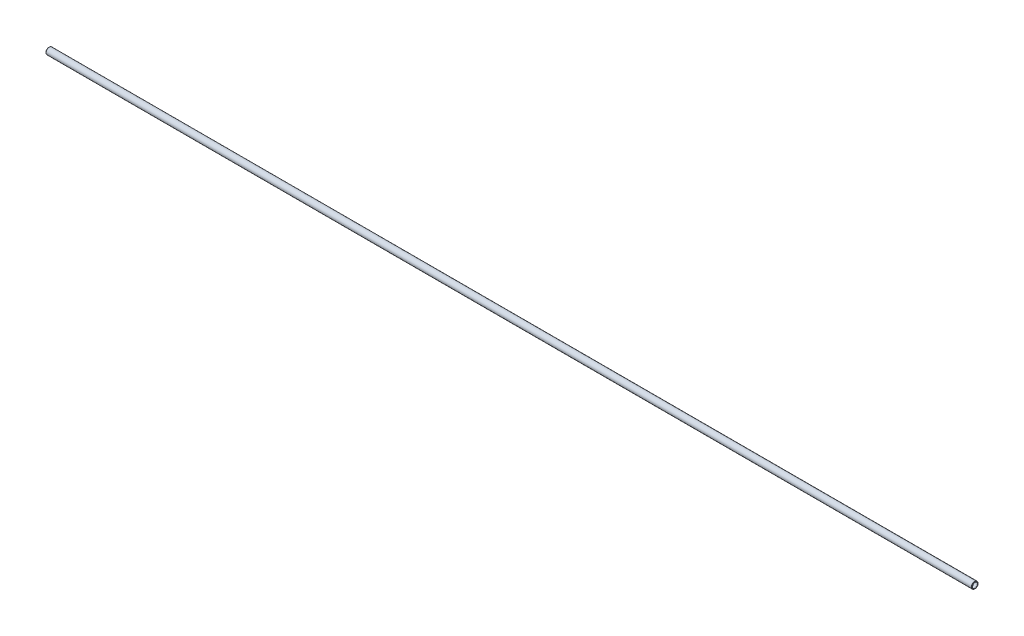
SolidWorks part; units mm, degrees
ref_plane "Front Plane" through (0, 0, 0) normal (0, 0, 1) x (1, 0, 0)
ref_plane "Top Plane" through (0, 0, 0) normal (0, 1, 0) x (1, 0, 0)
ref_plane "Right Plane" through (0, 0, 0) normal (1, 0, 0) x (0, 0, -1)
ref_plane "Plane1" through (1288.796, 0, 0) normal (1, 0, 0) x (0, 0, -1)
sketch "Sketch1" plane through (0, 0, 0) normal (0, 0, 1) x (1, 0, 0)
  line L0 (-0.445, 3.6899) -> (-0.2794, 3.5242)
  line L1 (-0.2794, 3.5242) -> (0, 3.5242)
  line L2 (0, 3.5242) -> (0.5588, 4.0831)
  line L3 (0.5588, 4.0831) -> (1288.2372, 4.0831)
  line L4 (1288.2372, 4.0831) -> (1288.796, 3.5242)
  line L5 (1288.796, 3.5242) -> (1289.0754, 3.5242)
  line L6 (1289.0754, 3.5242) -> (1289.241, 3.6899)
  line L7 (1289.241, 3.8695) -> (1288.7149, 4.3956)
  line L8 (1288.3198, 4.5593) -> (0.4762, 4.5593)
  line L9 (0.0811, 4.3956) -> (-0.445, 3.8695)
  line L10 (1288.796, 0) -> (0, 0) construction
  arc A0 (-0.445, 3.8695) -> (-0.445, 3.6899) centre (-0.3552, 3.7797) ccw
  arc A1 (1289.241, 3.6899) -> (1289.241, 3.8695) centre (1289.1512, 3.7797) ccw
  arc A2 (1288.7149, 4.3956) -> (1288.3198, 4.5593) centre (1288.3198, 4.0005) ccw
  arc A3 (0.4762, 4.5593) -> (0.0811, 4.3956) centre (0.4763, 4.0005) ccw
revolve "Revolve1" add sketch "Sketch1" angle 360 about L10 reverse direction yes
ref_plane "Plane2" through (644.398, 0, 0) normal (1, 0, 0) x (0, 0, -1)
ref_plane "cp1 XY" through (644.398, 0, 0) normal (1, 0, 0) x (0, 0, -1)
ref_plane "cp1 XZ" through (0, 4.5593, 0) normal (0, -1, 0) x (-1, 0, 0)
ref_plane "cp1 YZ" through (0, 0, 0) normal (0, 0, -1) x (-1, 0, 0)
ref_axis "cp1 X" through (644.398, 4.5593, 80.9) along (0, 0, -1)
ref_axis "cp1 Y" through (644.398, -50, 0) along (0, 1, 0)
ref_axis "cp1 Z" through (80.9, 4.5593, 0) along (-1, 0, 0)
sketch3d "cp1"
  point P0 (644.398, 4.5593, 0)
ref_plane "cp2 XY" through (644.398, 0, 0) normal (1, 0, 0) x (0, 0, -1)
ref_plane "cp2 XZ" through (0, 0, 0) normal (0, -1, 0) x (-1, 0, 0)
ref_plane "cp2 YZ" through (0, 0, -4.5593) normal (0, 0, -1) x (-1, 0, 0)
ref_axis "cp2 X" through (644.398, 0, 80.9) along (0, 0, -1)
ref_axis "cp2 Y" through (644.398, -50, -4.5593) along (0, 1, 0)
ref_axis "cp2 Z" through (80.9, 0, -4.5593) along (-1, 0, 0)
sketch3d "cp2"
  point P0 (644.398, 0, -4.5593)
ref_plane "cp3 XY" through (644.398, 0, 0) normal (1, 0, 0) x (0, 0, -1)
ref_plane "cp3 XZ" through (0, -4.5593, 0) normal (0, -1, 0) x (-1, 0, 0)
ref_plane "cp3 YZ" through (0, 0, 0) normal (0, 0, -1) x (-1, 0, 0)
ref_axis "cp3 X" through (644.398, -4.5593, 80.9) along (0, 0, -1)
ref_axis "cp3 Y" through (644.398, -50, 0) along (0, 1, 0)
ref_axis "cp3 Z" through (80.9, -4.5593, 0) along (-1, 0, 0)
sketch3d "cp3"
  point P0 (644.398, -4.5593, 0)
ref_plane "cp4 XY" through (644.398, 0, 0) normal (1, 0, 0) x (0, 0, -1)
ref_plane "cp4 XZ" through (0, 0, 0) normal (0, -1, 0) x (-1, 0, 0)
ref_plane "cp4 YZ" through (0, 0, 4.5593) normal (0, 0, -1) x (-1, 0, 0)
ref_axis "cp4 X" through (644.398, 0, 80.9) along (0, 0, -1)
ref_axis "cp4 Y" through (644.398, -50, 4.5593) along (0, 1, 0)
ref_axis "cp4 Z" through (80.9, 0, 4.5593) along (-1, 0, 0)
sketch3d "cp4"
  point P0 (644.398, 0, 4.5593)
ref_plane "tube_front XY" through (0, 0, 0) normal (1, 0, 0) x (0, 0, -1)
ref_plane "tube_front XZ" through (0, 0, 0) normal (0, -1, 0) x (-1, 0, 0)
ref_plane "tube_front YZ" through (0, 0, 0) normal (0, 0, -1) x (-1, 0, 0)
ref_axis "tube_front X" through (0, 0, 80.9) along (0, 0, -1)
ref_axis "tube_front Y" through (0, -50, 0) along (0, 1, 0)
ref_axis "tube_front Z" through (80.9, 0, 0) along (-1, 0, 0)
sketch3d "tube_front"
  point P0 (0, 0, 0)
ref_plane "tube_rear XY" through (1288.796, 0, 0) normal (1, 0, 0) x (0, 0, -1)
ref_plane "tube_rear XZ" through (0, 0, 0) normal (0, -1, 0) x (-1, 0, 0)
ref_plane "tube_rear YZ" through (0, 0, 0) normal (0, 0, -1) x (-1, 0, 0)
ref_axis "tube_rear X" through (1288.796, 0, 80.9) along (0, 0, -1)
ref_axis "tube_rear Y" through (1288.796, -50, 0) along (0, 1, 0)
ref_axis "tube_rear Z" through (80.9, 0, 0) along (-1, 0, 0)
sketch3d "tube_rear"
  point P0 (1288.796, 0, 0)
